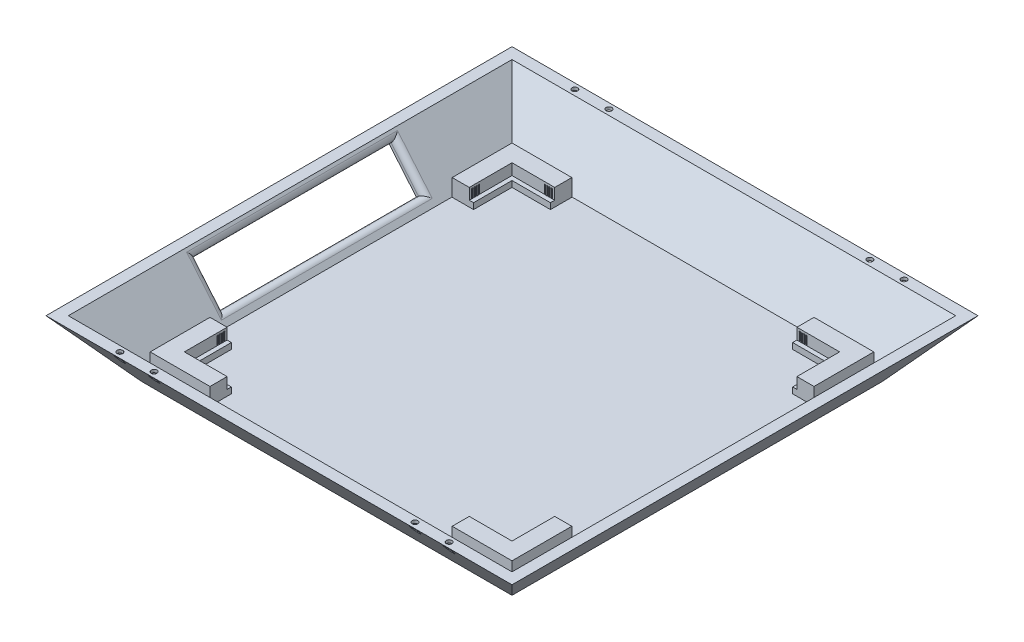
SolidWorks part; units mm, degrees
ref_plane "Front Plane" through (0, 0, 0) normal (0, 0, 1) x (1, 0, 0)
ref_plane "Top Plane" through (0, 0, 0) normal (0, 1, 0) x (1, 0, 0)
ref_plane "Right Plane" through (0, 0, 0) normal (1, 0, 0) x (0, 0, -1)
sketch "Sketch1" plane through (0, 0, 0) normal (0, 1, 0) x (1, 0, 0)
  line L1 (-65, -65) -> (65, -65)
  line L2 (-65, -65) -> (-65, 65)
  line L3 (-65, 65) -> (65, 65)
  line L4 (65, -65) -> (65, 65)
  line L5 (-65, -65) -> (65, 65) construction
  line L6 (-65, 65) -> (65, -65) construction
  point P0 (0, 0)
  dimension "D1" = 130
  dimension "D2" = 130
extrude "Boss-Extrude1" add sketch "Sketch1" along normal blind 20 draft 40 draft outward yes
shell "Shell1" thickness 3 removed face at (0, 20, 0)
sketch "Sketch2" plane through (0, 3, 0) normal (0, 1, 0) x (1, 0, 0)
  line L1 (-57.5, -57.5) -> (57.5, -57.5)
  line L2 (-57.5, -57.5) -> (-57.5, 57.5)
  line L3 (-57.5, 57.5) -> (57.5, 57.5)
  line L4 (57.5, -57.5) -> (57.5, 57.5)
  line L5 (-57.5, -57.5) -> (57.5, 57.5) construction
  line L6 (-57.5, 57.5) -> (57.5, -57.5) construction
  line L7 (57.5, 57.5) -> (42.5, 57.5)
  line L8 (57.5, 57.5) -> (57.5, 42.5)
  line L9 (57.5, 42.5) -> (42.5, 42.5)
  line L10 (42.5, 57.5) -> (42.5, 42.5)
  line L11 (-57.5, 57.5) -> (-42.5, 57.5)
  line L12 (-57.5, 57.5) -> (-57.5, 42.5)
  line L13 (-57.5, 42.5) -> (-42.5, 42.5)
  line L14 (-42.5, 57.5) -> (-42.5, 42.5)
  line L15 (-57.5, -57.5) -> (-42.5, -57.5)
  line L16 (-57.5, -57.5) -> (-57.5, -42.5)
  line L17 (-57.5, -42.5) -> (-42.5, -42.5)
  line L18 (-42.5, -57.5) -> (-42.5, -42.5)
  line L19 (57.5, -57.5) -> (42.5, -57.5)
  line L20 (57.5, -57.5) -> (57.5, -42.5)
  line L21 (57.5, -42.5) -> (42.5, -42.5)
  line L22 (42.5, -57.5) -> (42.5, -42.5)
  line L23 (42.5, -57.5) -> (57.5, -57.5)
  line L24 (42.5, -57.5) -> (42.5, -63.5)
  line L25 (42.5, -63.5) -> (57.5, -63.5)
  line L26 (57.5, -57.5) -> (57.5, -63.5)
  line L27 (57.5, -42.5) -> (63.5, -42.5)
  line L28 (57.5, -42.5) -> (57.5, -63.5)
  line L29 (57.5, -63.5) -> (63.5, -63.5)
  line L30 (63.5, -42.5) -> (63.5, -63.5)
  line L31 (-57.5, -57.5) -> (-42.5, -57.5)
  line L32 (-57.5, -57.5) -> (-57.5, -63.5)
  line L33 (-57.5, -63.5) -> (-42.5, -63.5)
  line L34 (-42.5, -57.5) -> (-42.5, -63.5)
  line L35 (-57.5, -42.5) -> (-63.5, -42.5)
  line L36 (-57.5, -42.5) -> (-57.5, -63.5)
  line L37 (-57.5, -63.5) -> (-63.5, -63.5)
  line L38 (-63.5, -42.5) -> (-63.5, -63.5)
  line L39 (42.5, 57.5) -> (57.5, 57.5)
  line L40 (42.5, 57.5) -> (42.5, 63.5)
  line L41 (42.5, 63.5) -> (57.5, 63.5)
  line L42 (57.5, 57.5) -> (57.5, 63.5)
  line L43 (57.5, 42.5) -> (63.5, 42.5)
  line L44 (57.5, 42.5) -> (57.5, 63.5)
  line L45 (57.5, 63.5) -> (63.5, 63.5)
  line L46 (63.5, 42.5) -> (63.5, 63.5)
  line L47 (-57.5, 57.5) -> (-42.5, 57.5)
  line L48 (-57.5, 57.5) -> (-57.5, 63.5)
  line L49 (-57.5, 63.5) -> (-42.5, 63.5)
  line L50 (-42.5, 57.5) -> (-42.5, 63.5)
  line L51 (-57.5, 42.5) -> (-63.5, 42.5)
  line L52 (-57.5, 42.5) -> (-57.5, 63.5)
  line L53 (-57.5, 63.5) -> (-63.5, 63.5)
  line L54 (-63.5, 42.5) -> (-63.5, 63.5)
  point P0 (0, 0)
  dimension "D1" = 115
  dimension "D2" = 115
  dimension "D3" = 15
  dimension "D4" = 15
  dimension "D5" = 15
  dimension "D6" = 15
  dimension "D7" = 6
  dimension "D8" = 6
  dimension "D9" = 6
  dimension "D10" = 6
  dimension "D11" = 6
  dimension "D12" = 6
  dimension "D13" = 6
  dimension "D14" = 6
extrude "Boss-Extrude2" add sketch "Sketch2" along normal blind 6 contours L54 L51 L2 L48 L53 | L3 L50 L49 L48 | L35 L38 L37 L32 L2 | L3 L42 L41 L40 | L43 L46 L45 L42 L4 | L34 L1 L32 L33 | L26 L1 L24 L25 | L30 L27 L4 L26 L29 region at (-60.5, 3, 53) region at (-50, 3, 60.5) region at (50, 3, 60.5) region at (-60.5, 3, -53) region at (60.5, 3, 53) region at (-50, 3, -60.5) region at (60.5, 3, -53) region at (50, 3, -60.5)
sketch "Sketch3" plane through (0, 3, 0) normal (0, 1, 0) x (1, 0, 0)
  line L1 (-57.5, -57.5) -> (57.5, -57.5)
  line L2 (-57.5, -57.5) -> (-57.5, 57.5)
  line L3 (-57.5, 57.5) -> (57.5, 57.5)
  line L4 (57.5, -57.5) -> (57.5, 57.5)
  line L5 (-57.5, -57.5) -> (57.5, 57.5) construction
  line L6 (-57.5, 57.5) -> (57.5, -57.5) construction
  line L7 (-57.5, 42.5) -> (-56, 42.5)
  line L8 (-57.5, 42.5) -> (-57.5, 57.5)
  line L9 (-57.5, 57.5) -> (-56, 57.5)
  line L10 (-56, 42.5) -> (-56, 57.5)
  line L11 (-42.5, 57.5) -> (-56, 57.5)
  line L12 (-42.5, 57.5) -> (-42.5, 56)
  line L13 (-42.5, 56) -> (-56, 56)
  line L14 (-56, 57.5) -> (-56, 56)
  line L15 (57.5, 42.5) -> (56, 42.5)
  line L16 (57.5, 42.5) -> (57.5, 57.5)
  line L17 (57.5, 57.5) -> (56, 57.5)
  line L18 (56, 42.5) -> (56, 57.5)
  line L19 (42.5, 57.5) -> (56, 57.5)
  line L20 (42.5, 57.5) -> (42.5, 56)
  line L21 (42.5, 56) -> (56, 56)
  line L22 (56, 57.5) -> (56, 56)
  line L23 (-57.5, -42.5) -> (-56, -42.5)
  line L24 (-57.5, -42.5) -> (-57.5, -57.5)
  line L25 (-57.5, -57.5) -> (-56, -57.5)
  line L26 (-56, -42.5) -> (-56, -57.5)
  line L27 (-42.5, -57.5) -> (-56, -57.5)
  line L28 (-42.5, -57.5) -> (-42.5, -56)
  line L29 (-42.5, -56) -> (-56, -56)
  line L30 (-56, -57.5) -> (-56, -56)
  line L31 (57.5, -42.5) -> (56, -42.5)
  line L32 (57.5, -42.5) -> (57.5, -57.5)
  line L33 (57.5, -57.5) -> (56, -57.5)
  line L34 (56, -42.5) -> (56, -57.5)
  line L35 (42.5, -57.5) -> (56, -57.5)
  line L36 (42.5, -57.5) -> (42.5, -56)
  line L37 (42.5, -56) -> (56, -56)
  line L38 (56, -57.5) -> (56, -56)
  point P0 (0, 0)
  line M10 (-57.5, -42.5) -> (-57.5, -57.5)
  line M11 (-57.5, -57.5) -> (-42.5, -57.5)
  line M24 (-57.5, 57.5) -> (-57.5, 42.5)
  line M25 (57.5, 57.5) -> (42.5, 57.5)
  line M30 (57.5, 42.5) -> (57.5, 57.5)
  line M33 (42.5, -57.5) -> (57.5, -57.5)
  line M34 (57.5, -57.5) -> (57.5, -42.5)
  dimension "D1" = 1.5
  dimension "D2" = 1.5
  dimension "D3" = 1.5
  dimension "D4" = 1.5
extrude "Boss-Extrude3" add sketch "Sketch3" along normal blind 2.1 contours L7 L10 L3 M24 | L20 L21 L18 L3 | L18 L15 M30 M25 | L26 L23 M10 M11 | L28 L29 L26 L1 | L37 L36 L34 M33 | L31 L34 L1 M34 | L11 L12 L13 L14 region at (-56.75, 3, 50) region at (-49.25, 3, 56.75) region at (-56.75, 3, -50) region at (49.25, 3, 56.75) region at (56.75, 3, 50) region at (49.25, 3, -56.75) region at (56.75, 3, -50)
sketch "Sketch4" plane through (0, 0, -57.5) normal (0, 0, 1) x (1, 0, 0)
  line L1 (-43.3, 8.25) -> (-43.7, 8.25)
  line L2 (-43.3, 8.25) -> (-43.3, 5.25)
  line L3 (-43.3, 5.25) -> (-43.7, 5.25)
  line L4 (-43.7, 8.25) -> (-43.7, 5.25)
  line L5 (-44.1, 8.25) -> (-44.5, 8.25)
  line L6 (-44.1, 8.25) -> (-44.1, 5.25)
  line L7 (-44.1, 5.25) -> (-44.5, 5.25)
  line L8 (-44.5, 8.25) -> (-44.5, 5.25)
  line L9 (-44.9, 8.25) -> (-45.3, 8.25)
  line L10 (-44.9, 8.25) -> (-44.9, 5.25)
  line L11 (-44.9, 5.25) -> (-45.3, 5.25)
  line L12 (-45.3, 8.25) -> (-45.3, 5.25)
  line L13 (-45.7, 8.25) -> (-46.1, 8.25)
  line L14 (-45.7, 8.25) -> (-45.7, 5.25)
  line L15 (-45.7, 5.25) -> (-46.1, 5.25)
  line L16 (-46.1, 8.25) -> (-46.1, 5.25)
  line L17 (-57.5, 9) -> (-42.5, 9) construction
  line L18 (-42.5, 9) -> (-42.5, 5.1) construction
  dimension "D1" = 0.4
  dimension "D2" = 0.4
  dimension "D3" = 0.4
  dimension "D4" = 0.4
  dimension "D5" = 3
  dimension "D6" = 3
  dimension "D7" = 3
  dimension "D8" = 3
  dimension "D9" = 0.75
  dimension "D10" = 0.75
  dimension "D11" = 0.75
  dimension "D12" = 0.75
  dimension "D13" = 0.8
  dimension "D14" = 0.4
  dimension "D15" = 0.4
  dimension "D16" = 0.4
extrude "Boss-Extrude4" add sketch "Sketch4" along normal blind 0.2
chamfer "Chamfer2" distance 0.15 angle 45 8 edges at (-43.3, 6.75, -57.3) (-43.7, 6.75, -57.3) (-44.1, 6.75, -57.3) (-44.5, 6.75, -57.3) (-44.9, 6.75, -57.3) (-45.3, 6.75, -57.3) (-45.7, 6.75, -57.3) (-46.1, 6.75, -57.3)
sketch "Sketch5" plane through (-57.5, 0, 0) normal (1, 0, 0) x (0, 0, -1)
  line L0 (42.5, 9) -> (42.5, 5.1) construction
  line L1 (43.3, 8.25) -> (43.7, 8.25)
  line L2 (43.3, 8.25) -> (43.3, 5.25)
  line L3 (43.3, 5.25) -> (43.7, 5.25)
  line L4 (43.7, 8.25) -> (43.7, 5.25)
  line L5 (42.5, 9) -> (57.5, 9) construction
  line L6 (44.1, 8.25) -> (44.1, 5.25)
  line L7 (44.1, 8.25) -> (44.5, 8.25)
  line L8 (44.5, 8.25) -> (44.5, 5.25)
  line L9 (44.1, 5.25) -> (44.5, 5.25)
  line L10 (44.9, 8.25) -> (44.9, 5.25)
  line L11 (44.9, 8.25) -> (45.3, 8.25)
  line L12 (45.3, 8.25) -> (45.3, 5.25)
  line L13 (44.9, 5.25) -> (45.3, 5.25)
  line L14 (45.7, 8.25) -> (45.7, 5.25)
  line L15 (45.7, 8.25) -> (46.1, 8.25)
  line L16 (46.1, 8.25) -> (46.1, 5.25)
  line L17 (45.7, 5.25) -> (46.1, 5.25)
  dimension "D1" = 0.4
  dimension "D2" = 3
  dimension "D3" = 0.8
  dimension "D4" = 0.75
  dimension "D5" = 4
extrude "Boss-Extrude5" add sketch "Sketch5" along normal blind 0.2
chamfer "Chamfer3" distance 0.15 angle 45 8 edges at (-57.3, 6.75, -46.1) (-57.3, 6.75, -45.7) (-57.3, 6.75, -45.3) (-57.3, 6.75, -44.9) (-57.3, 6.75, -44.1) (-57.3, 6.75, -44.5) (-57.3, 6.75, -43.7) (-57.3, 6.75, -43.3)
sketch "Sketch6" plane through (-57.5, 0, 0) normal (1, 0, 0) x (0, 0, -1)
  line L0 (-42.5, 9) -> (-42.5, 5.1) construction
  line L1 (-43.3, 8.25) -> (-43.7, 8.25)
  line L2 (-43.3, 8.25) -> (-43.3, 5.25)
  line L3 (-43.3, 5.25) -> (-43.7, 5.25)
  line L4 (-43.7, 8.25) -> (-43.7, 5.25)
  line L5 (-42.5, 9) -> (-57.5, 9) construction
  line L6 (-44.1, 8.25) -> (-44.1, 5.25)
  line L7 (-44.1, 8.25) -> (-44.5, 8.25)
  line L8 (-44.5, 8.25) -> (-44.5, 5.25)
  line L9 (-44.1, 5.25) -> (-44.5, 5.25)
  line L10 (-44.9, 8.25) -> (-44.9, 5.25)
  line L11 (-44.9, 8.25) -> (-45.3, 8.25)
  line L12 (-45.3, 8.25) -> (-45.3, 5.25)
  line L13 (-44.9, 5.25) -> (-45.3, 5.25)
  line L14 (-45.7, 8.25) -> (-45.7, 5.25)
  line L15 (-45.7, 8.25) -> (-46.1, 8.25)
  line L16 (-46.1, 8.25) -> (-46.1, 5.25)
  line L17 (-45.7, 5.25) -> (-46.1, 5.25)
  dimension "D1" = 0.4
  dimension "D2" = 3
  dimension "D3" = 0.8
  dimension "D4" = 0.75
  dimension "D5" = 4
extrude "Boss-Extrude6" add sketch "Sketch6" along normal blind 0.2
chamfer "Chamfer4" distance 0.15 angle 45 8 edges at (-57.3, 6.75, 44.5) (-57.3, 6.75, 44.1) (-57.3, 6.75, 43.3) (-57.3, 6.75, 43.7) (-57.3, 6.75, 44.9) (-57.3, 6.75, 45.3) (-57.3, 6.75, 45.7) (-57.3, 6.75, 46.1)
sketch "Sketch7" plane through (0, 0, 57.5) normal (0, 0, -1) x (-1, 0, 0)
  line L0 (42.5, 9) -> (42.5, 5.1) construction
  line L1 (43.3, 8.25) -> (43.7, 8.25)
  line L2 (43.3, 8.25) -> (43.3, 5.25)
  line L3 (43.3, 5.25) -> (43.7, 5.25)
  line L4 (43.7, 8.25) -> (43.7, 5.25)
  line L5 (57.5, 9) -> (42.5, 9) construction
  line L6 (44.1, 8.25) -> (44.1, 5.25)
  line L7 (44.1, 8.25) -> (44.5, 8.25)
  line L8 (44.5, 8.25) -> (44.5, 5.25)
  line L9 (44.1, 5.25) -> (44.5, 5.25)
  line L10 (44.9, 8.25) -> (44.9, 5.25)
  line L11 (44.9, 8.25) -> (45.3, 8.25)
  line L12 (45.3, 8.25) -> (45.3, 5.25)
  line L13 (44.9, 5.25) -> (45.3, 5.25)
  line L14 (45.7, 8.25) -> (45.7, 5.25)
  line L15 (45.7, 8.25) -> (46.1, 8.25)
  line L16 (46.1, 8.25) -> (46.1, 5.25)
  line L17 (45.7, 5.25) -> (46.1, 5.25)
  dimension "D1" = 3
  dimension "D2" = 0.4
  dimension "D3" = 0.8
  dimension "D4" = 0.75
  dimension "D5" = 4
extrude "Boss-Extrude7" add sketch "Sketch7" along normal blind 0.2
chamfer "Chamfer5" distance 0.15 angle 45 8 edges at (-46.1, 6.75, 57.3) (-45.7, 6.75, 57.3) (-44.9, 6.75, 57.3) (-45.3, 6.75, 57.3) (-44.5, 6.75, 57.3) (-44.1, 6.75, 57.3) (-43.7, 6.75, 57.3) (-43.3, 6.75, 57.3)
sketch "Sketch8" plane through (57.5, 0, 0) normal (-1, 0, 0) x (0, 0, 1)
  line L0 (57.5, 9) -> (42.5, 9) construction
  line L1 (43.3, 8.25) -> (43.7, 8.25)
  line L2 (43.3, 8.25) -> (43.3, 5.25)
  line L3 (43.3, 5.25) -> (43.7, 5.25)
  line L4 (43.7, 8.25) -> (43.7, 5.25)
  line L5 (42.5, 9) -> (42.5, 5.1) construction
  line L6 (44.1, 8.25) -> (44.1, 5.25)
  line L7 (44.1, 8.25) -> (44.5, 8.25)
  line L8 (44.5, 8.25) -> (44.5, 5.25)
  line L9 (44.1, 5.25) -> (44.5, 5.25)
  line L10 (44.9, 8.25) -> (44.9, 5.25)
  line L11 (44.9, 8.25) -> (45.3, 8.25)
  line L12 (45.3, 8.25) -> (45.3, 5.25)
  line L13 (44.9, 5.25) -> (45.3, 5.25)
  line L14 (45.7, 8.25) -> (45.7, 5.25)
  line L15 (45.7, 8.25) -> (46.1, 8.25)
  line L16 (46.1, 8.25) -> (46.1, 5.25)
  line L17 (45.7, 5.25) -> (46.1, 5.25)
  dimension "D1" = 3
  dimension "D2" = 0.4
  dimension "D3" = 0.75
  dimension "D4" = 0.8
  dimension "D5" = 4
extrude "Boss-Extrude8" add sketch "Sketch8" along normal blind 0.2
chamfer "Chamfer6" distance 0.15 angle 45 8 edges at (57.3, 6.75, 46.1) (57.3, 6.75, 45.7) (57.3, 6.75, 45.3) (57.3, 6.75, 44.9) (57.3, 6.75, 44.5) (57.3, 6.75, 44.1) (57.3, 6.75, 43.7) (57.3, 6.75, 43.3)
sketch "Sketch9" plane through (0, 0, 57.5) normal (0, 0, -1) x (-1, 0, 0)
  line L0 (-42.5, 9) -> (-42.5, 5.1) construction
  line L1 (-43.25, 8.25) -> (-43.65, 8.25)
  line L2 (-43.25, 8.25) -> (-43.25, 5.25)
  line L3 (-43.25, 5.25) -> (-43.65, 5.25)
  line L4 (-43.65, 8.25) -> (-43.65, 5.25)
  line L5 (-42.5, 9) -> (-57.5, 9) construction
  line L6 (-44.05, 8.25) -> (-44.05, 5.25)
  line L7 (-44.05, 8.25) -> (-44.45, 8.25)
  line L8 (-44.45, 8.25) -> (-44.45, 5.25)
  line L9 (-44.05, 5.25) -> (-44.45, 5.25)
  line L10 (-44.85, 8.25) -> (-44.85, 5.25)
  line L11 (-44.85, 8.25) -> (-45.25, 8.25)
  line L12 (-45.25, 8.25) -> (-45.25, 5.25)
  line L13 (-44.85, 5.25) -> (-45.25, 5.25)
  line L14 (-45.65, 8.25) -> (-45.65, 5.25)
  line L15 (-45.65, 8.25) -> (-46.05, 8.25)
  line L16 (-46.05, 8.25) -> (-46.05, 5.25)
  line L17 (-45.65, 5.25) -> (-46.05, 5.25)
  dimension "D1" = 0.4
  dimension "D2" = 3
  dimension "D3" = 0.75
  dimension "D4" = 0.75
  dimension "D5" = 4
extrude "Boss-Extrude9" add sketch "Sketch9" along normal blind 0.2
chamfer "Chamfer7" distance 0.15 angle 45 8 edges at (43.25, 6.75, 57.3) (43.65, 6.75, 57.3) (44.05, 6.75, 57.3) (44.45, 6.75, 57.3) (44.85, 6.75, 57.3) (45.25, 6.75, 57.3) (45.65, 6.75, 57.3) (46.05, 6.75, 57.3)
sketch "Sketch10" plane through (0, 0, -57.5) normal (0, 0, 1) x (1, 0, 0)
  line L0 (42.5, 9) -> (42.5, 5.1) construction
  line L1 (43.3, 8.25) -> (43.7, 8.25)
  line L2 (43.3, 8.25) -> (43.3, 5.25)
  line L3 (43.3, 5.25) -> (43.7, 5.25)
  line L4 (43.7, 8.25) -> (43.7, 5.25)
  line L5 (42.5, 9) -> (57.5, 9) construction
  line L6 (44.1, 8.25) -> (44.1, 5.25)
  line L7 (44.1, 8.25) -> (44.5, 8.25)
  line L8 (44.5, 8.25) -> (44.5, 5.25)
  line L9 (44.1, 5.25) -> (44.5, 5.25)
  line L10 (44.9, 8.25) -> (44.9, 5.25)
  line L11 (44.9, 8.25) -> (45.3, 8.25)
  line L12 (45.3, 8.25) -> (45.3, 5.25)
  line L13 (44.9, 5.25) -> (45.3, 5.25)
  line L14 (45.7, 8.25) -> (45.7, 5.25)
  line L15 (45.7, 8.25) -> (46.1, 8.25)
  line L16 (46.1, 8.25) -> (46.1, 5.25)
  line L17 (45.7, 5.25) -> (46.1, 5.25)
  dimension "D1" = 3
  dimension "D2" = 0.4
  dimension "D3" = 0.8
  dimension "D4" = 0.75
  dimension "D5" = 4
extrude "Boss-Extrude10" add sketch "Sketch10" along normal blind 0.2
chamfer "Chamfer8" distance 0.15 angle 45 8 edges at (46.1, 6.75, -57.3) (45.7, 6.75, -57.3) (45.3, 6.75, -57.3) (44.9, 6.75, -57.3) (44.5, 6.75, -57.3) (44.1, 6.75, -57.3) (43.7, 6.75, -57.3) (43.3, 6.75, -57.3)
sketch "Sketch11" plane through (57.5, 0, 0) normal (-1, 0, 0) x (0, 0, 1)
  line L0 (-42.5, 9) -> (-57.5, 9) construction
  line L1 (-43.7, 8.25) -> (-43.3, 8.25)
  line L2 (-43.7, 8.25) -> (-43.7, 5.25)
  line L3 (-43.7, 5.25) -> (-43.3, 5.25)
  line L4 (-43.3, 8.25) -> (-43.3, 5.25)
  line L5 (-42.5, 9) -> (-42.5, 5.1) construction
  line L6 (-44.5, 8.25) -> (-44.5, 5.25)
  line L7 (-44.5, 8.25) -> (-44.1, 8.25)
  line L8 (-44.1, 8.25) -> (-44.1, 5.25)
  line L9 (-44.5, 5.25) -> (-44.1, 5.25)
  line L10 (-45.3, 8.25) -> (-45.3, 5.25)
  line L11 (-45.3, 8.25) -> (-44.9, 8.25)
  line L12 (-44.9, 8.25) -> (-44.9, 5.25)
  line L13 (-45.3, 5.25) -> (-44.9, 5.25)
  line L14 (-46.1, 8.25) -> (-46.1, 5.25)
  line L15 (-46.1, 8.25) -> (-45.7, 8.25)
  line L16 (-45.7, 8.25) -> (-45.7, 5.25)
  line L17 (-46.1, 5.25) -> (-45.7, 5.25)
  dimension "D1" = 0.4
  dimension "D2" = 3
  dimension "D3" = 0.75
  dimension "D4" = 0.8
  dimension "D5" = 4
extrude "Boss-Extrude11" add sketch "Sketch11" along normal blind 0.2
chamfer "Chamfer9" distance 0.15 angle 45 8 edges at (57.3, 6.75, -43.3) (57.3, 6.75, -43.7) (57.3, 6.75, -44.1) (57.3, 6.75, -44.5) (57.3, 6.75, -44.9) (57.3, 6.75, -45.3) (57.3, 6.75, -45.7) (57.3, 6.75, -46.1)
sketch "Sketch13" plane through (-38.1436, -32.0063, 0) normal (-0.766, -0.6428, 0) x (0, 0, 1)
  line L1 (-35, 47.3343) -> (35, 47.3343)
  line L2 (-35, 47.3343) -> (-35, 62.3343)
  line L3 (-35, 62.3343) -> (35, 62.3343)
  line L4 (35, 47.3343) -> (35, 62.3343)
  line L5 (-35, 47.3343) -> (35, 62.3343) construction
  line L6 (-35, 62.3343) -> (35, 47.3343) construction
  line L7 (-81.782, 67.8893) -> (81.782, 67.8893) construction
  point P0 (0, 54.8343)
  dimension "D1" = 15
  dimension "D2" = 5.555
  dimension "D3" = 70
  dimension "D4" = 30
extrude "Cut-Extrude2" cut sketch "Sketch13" against normal blind 3.2
fillet "Fillet1" radius 2 4 edges at (-71.0923, 11.9277, -35) (-66.2714, 6.1823, 0) (-75.9132, 17.673, 0) (-71.0923, 11.9277, 35)
sketch "Sketch22" plane through (0, 20, 0) normal (0, 1, 0) x (1, 0, 0)
  line L0 (-77.8658, -77.8658) -> (77.8658, -77.8658) construction
  line L1 (-61.782, -77.8658) -> (-41.782, -77.8658)
  line L2 (-61.782, -77.8658) -> (-61.782, -81.782)
  line L3 (-61.782, -81.782) -> (-41.782, -81.782)
  line L4 (-41.782, -77.8658) -> (-41.782, -81.782)
  line L5 (-81.782, -81.782) -> (81.782, -81.782) construction
  line L6 (-81.782, 81.782) -> (-81.782, -81.782) construction
  line L7 (81.782, 81.782) -> (-81.782, 81.782) construction
  line L8 (-61.782, 81.782) -> (-41.782, 81.782)
  line L9 (-61.782, 81.782) -> (-61.782, 77.8658)
  line L10 (-61.782, 77.8658) -> (-41.782, 77.8658)
  line L11 (-41.782, 81.782) -> (-41.782, 77.8658)
  line L12 (77.8658, 77.8658) -> (-77.8658, 77.8658) construction
  line L13 (-81.782, -81.782) -> (81.782, -81.782) construction
  line L14 (61.782, -81.782) -> (41.782, -81.782)
  line L15 (61.782, -81.782) -> (61.782, -77.8658)
  line L16 (61.782, -77.8658) -> (41.782, -77.8658)
  line L17 (41.782, -81.782) -> (41.782, -77.8658)
  line L18 (-77.8658, -77.8658) -> (77.8658, -77.8658) construction
  line L19 (81.782, -81.782) -> (81.782, 81.782) construction
  line L20 (77.8658, 77.8658) -> (-77.8658, 77.8658) construction
  line L21 (61.782, 77.8658) -> (41.782, 77.8658)
  line L22 (61.782, 77.8658) -> (61.782, 81.782)
  line L23 (61.782, 81.782) -> (41.782, 81.782)
  line L24 (41.782, 77.8658) -> (41.782, 81.782)
  line L25 (81.782, 81.782) -> (-81.782, 81.782) construction
  circle A0 centre (-57.782, -79.8255) radius 1
  circle A1 centre (-45.782, -79.8255) radius 1
  circle A2 centre (-57.782, 79.822) radius 1
  circle A3 centre (-45.782, 79.822) radius 1
  circle A4 centre (57.782, -79.8255) radius 1
  circle A5 centre (45.782, -79.8255) radius 1
  circle A6 centre (57.782, 79.822) radius 1
  circle A7 centre (45.782, 79.822) radius 1
  point P18 (-61.782, 79.8239)
  dimension "D5" = 12
  dimension "D9" = 12
  dimension "D17" = 12
  dimension "D21" = 12
  dimension "D1" = 20
  dimension "D2" = 20
  dimension "D3" = 20
  dimension "D4" = 20
  dimension "D6" = 1.9598
  dimension "D7" = 1.9598
  dimension "D8" = 4
  dimension "D10" = 1.96
  dimension "D11" = 1.96
  dimension "D12" = 4
  dimension "D13" = 20
  dimension "D14" = 20
  dimension "D15" = 20
  dimension "D16" = 20
  dimension "D18" = 1.9598
  dimension "D19" = 1.9598
  dimension "D20" = 4
  dimension "D22" = 1.9562
  dimension "D23" = 1.9562
  dimension "D24" = 4
extrude "Cut-Extrude3" cut sketch "Sketch22" against normal blind 21.65 contours A0
extrude "Cut-Extrude4" cut sketch "Sketch22<5>" against normal blind 21.65 contours A1
sketch "Sketch22<5>" plane through (0, 20, 0) normal (0, 1, 0) x (1, 0, 0) same geometry as "Sketch22"
extrude "Cut-Extrude5" cut sketch "Sketch22<6>" against normal blind 21.65 contours A3
sketch "Sketch22<6>" plane through (0, 20, 0) normal (0, 1, 0) x (1, 0, 0) same geometry as "Sketch22"
extrude "Cut-Extrude6" cut sketch "Sketch22<7>" against normal blind 21.65 contours A2
sketch "Sketch22<7>" plane through (0, 20, 0) normal (0, 1, 0) x (1, 0, 0) same geometry as "Sketch22"
extrude "Cut-Extrude8" cut sketch "Sketch22<8>" against normal blind 10 contours A5
sketch "Sketch22<8>" plane through (0, 20, 0) normal (0, 1, 0) x (1, 0, 0) same geometry as "Sketch22"
extrude "Cut-Extrude9" cut sketch "Sketch22<9>" against normal blind 10 contours A4
sketch "Sketch22<9>" plane through (0, 20, 0) normal (0, 1, 0) x (1, 0, 0) same geometry as "Sketch22"
extrude "Cut-Extrude10" cut sketch "Sketch22<10>" against normal blind 10 contours A6
sketch "Sketch22<10>" plane through (0, 20, 0) normal (0, 1, 0) x (1, 0, 0) same geometry as "Sketch22"
extrude "Cut-Extrude11" cut sketch "Sketch22<11>" against normal blind 10 contours A7
sketch "Sketch22<11>" plane through (0, 20, 0) normal (0, 1, 0) x (1, 0, 0) same geometry as "Sketch22"
sketch3d "3DSketch3"
  circle A0 centre (-45.782, 10, -79.8195) radius 1.5
  circle A1 centre (-57.7765, 10, -79.8195) radius 1.5
  circle A2 centre (-45.782, 10, 79.8801) radius 1.5
  circle A3 centre (-57.7765, 10, 79.8801) radius 1.5
  point P2 (-45.782, 11.5, -79.8195)
  point P5 (-57.7765, 11.5, -79.8195)
  point P8 (-45.782, 11.5, 79.8801)
  point P11 (-57.7765, 11.5, 79.8801)
  dimension "D2" = 3
  dimension "D3" = 3
  dimension "D5" = 3
  dimension "D1" = 10
extrude "Cut-Extrude7" cut sketch "3DSketch3" along direction (0, -1, 0) on the side against the normal blind 9
sketch "Sketch23" plane through (0, 0, 0) normal (0, 1, 0) x (1, 0, 0)
  circle A0 centre (57.782, 79.822) radius 1.5
  circle A1 centre (45.782, 79.822) radius 1.5
  circle A2 centre (45.782, -79.8255) radius 1.5
  circle A3 centre (57.782, -79.8255) radius 1.5
  point P6 (58.5352, -78.8334)
  point P7 (57.7987, -78.8334)
  point P8 (43.9616, -78.8334)
  point P9 (45.8226, -78.8334)
  point P11 (45.782, -79.8255)
  point P13 (57.782, -79.8255)
extrude "Cut-Extrude12" cut sketch "Sketch23" along normal blind 19
